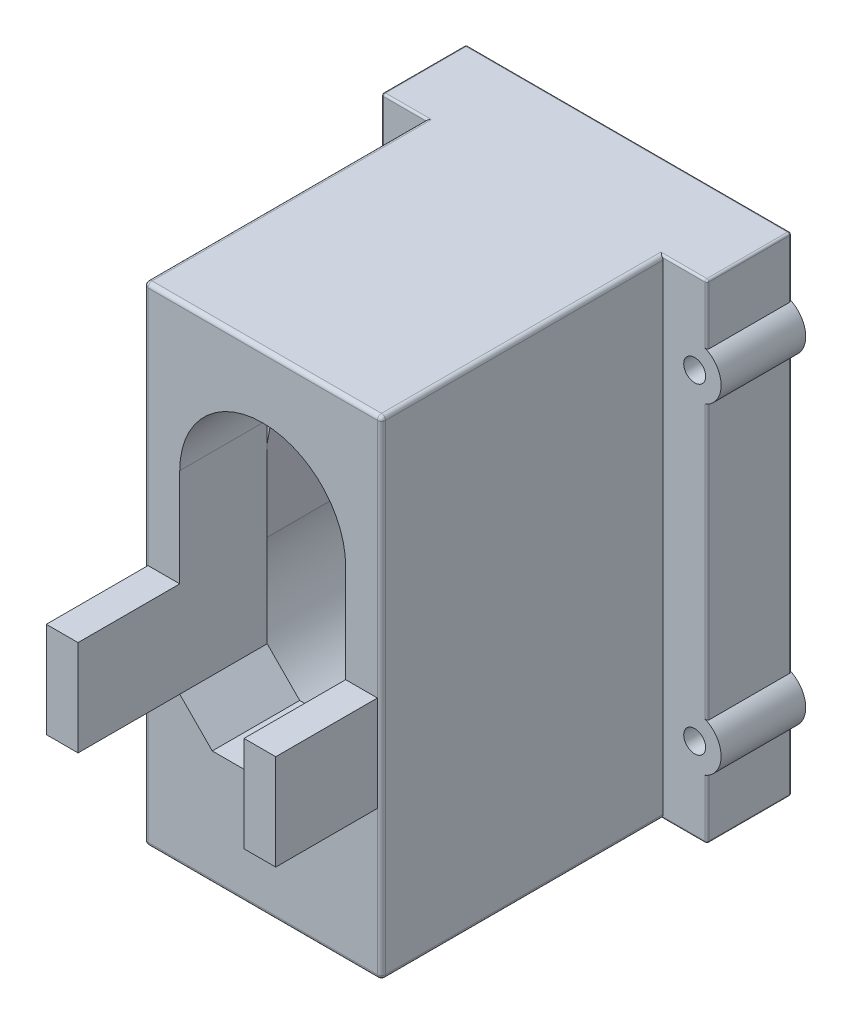
SolidWorks part; units mm, degrees
ref_plane "Plan de face" through (0, 0, 0) normal (0, 0, 1) x (1, 0, 0)
ref_plane "Plan de dessus" through (0, 0, 0) normal (0, 1, 0) x (1, 0, 0)
ref_plane "Plan de droite" through (0, 0, 0) normal (1, 0, 0) x (0, 0, -1)
sketch "Esquisse1" plane through (0, 0, 0) normal (0, 0, 1) x (1, 0, 0)
  line L0 (-4.8779, 36.0098) -> (-4.8779, -83.9902) construction
  line L1 (-44.8779, 36.0098) -> (35.1221, 36.0098)
  line L2 (-44.8779, 36.0098) -> (-44.8779, -83.9902)
  line L3 (-44.8779, -83.9902) -> (35.1221, -83.9902)
  line L4 (35.1221, 36.0098) -> (35.1221, -83.9902)
  dimension "D1" = 120
  dimension "D2" = 80
extrude "Boss.-Extru.1" add sketch "Esquisse1" along normal blind 90
sketch "Esquisse2" plane through (0, 0, 90) normal (0, 0, 1) x (1, 0, 0)
  line L0 (-4.8779, -83.9902) -> (-4.8779, 36.0098) construction
  line L1 (-44.8779, -83.9902) -> (35.1221, -83.9902) construction
  line L2 (35.1221, 36.0098) -> (-44.8779, 36.0098) construction
  line L3 (-25.2779, 0) -> (-25.2779, -47.5972)
  line L4 (15.5221, 0) -> (15.5221, -47.5972)
  line L5 (-4.8779, -55.6672) -> (7.5221, -55.6672)
  line L6 (-4.8779, -55.6672) -> (-17.2779, -55.6672)
  line L7 (15.5221, -47.5972) -> (7.5221, -55.6672)
  line L8 (-25.2779, -47.5972) -> (-17.2779, -55.6672)
  circle A0 centre (-4.8779, 0) radius 20.4
  dimension "D1" = 40.8
  dimension "D2" = 24.8
  dimension "D3" = 8.07
  dimension "D4" = 8.07
extrude "Enlèv. mat.-Extru.1" cut sketch "Esquisse2" against normal blind 21.5 contours L0 A0 | A0 L0 | L6 L0 A0 L3 L8 | L0 L5 L7 L4 A0 region at (-15.4138, -34.8601, 90) region at (5.658, -34.8601, 90) region at (-13.5359, 0, 90) region at (3.7801, 0, 90)
sketch "Esquisse3" plane through (0, 0, 68.5) normal (0, 0, 1) x (1, 0, 0)
  line L0 (-25.2779, 0) -> (15.5221, 0) construction
  line L1 (-4.8779, 0) -> (-4.8779, -55.6672) construction
  line L2 (-17.2779, -55.6672) -> (7.5221, -55.6672) construction
  line L3 (-24.3779, 0) -> (-29.6983, -29.3249)
  line L4 (14.6221, 0) -> (19.9425, -29.3249)
  circle A0 centre (-4.8779, 0) radius 19.5
  circle A1 centre (-4.8779, -36.7247) radius 25.9
  line M3 (-25.2779, 0) -> (-25.2779, -47.5972)
  line M4 (-25.2779, -47.5972) -> (-17.2779, -55.6672)
  line M5 (-17.2779, -55.6672) -> (7.5221, -55.6672)
  line M6 (7.5221, -55.6672) -> (15.5221, -47.5972)
  line M7 (15.5221, -47.5972) -> (15.5221, 0)
  dimension "D1" = 39
  dimension "D2" = 51.8
extrude "Enlèv. mat.-Extru.7" cut sketch "Esquisse3" against normal through all contours A1 A0 | A1 A0 L3 M3 | A0 A1 | A1 L3 M3 | A1 A0 M7 M3 M4 M5 M6 | A1 M7 M6 M5 M4 M3 | A1 L4 A0 M7 | A1 L4 M7 region at (-23.1117, -12.3273, 68.5) region at (-4.8779, 2.2509, 68.5) region at (-26.6699, -17.7509, 68.5) region at (13.356, -12.3273, 68.5) region at (-4.8779, -15.0342, 68.5) region at (-4.8779, -35.9109, 68.5) region at (-27.2977, -25.1442, 68.5) region at (16.9142, -17.7509, 68.5)
sketch "Esquisse4" plane through (0, 36.0098, 0) normal (0, 1, 0) x (1, 0, 0)
  line L0 (-44.8779, -90) -> (-44.8779, 0) construction
  line L1 (-44.8779, -20.8) -> (-34.0779, -20.8)
  line L2 (-44.8779, -20.8) -> (-44.8779, -90)
  line L3 (-44.8779, -90) -> (-34.0779, -90)
  line L4 (-34.0779, -20.8) -> (-34.0779, -90)
  line L5 (35.1221, -90) -> (-44.8779, -90) construction
  line L6 (35.1221, -90) -> (35.1221, 0) construction
  line L7 (35.1221, -20.8) -> (24.3221, -20.8)
  line L8 (35.1221, -20.8) -> (35.1221, -90)
  line L9 (35.1221, -90) -> (24.3221, -90)
  line L10 (24.3221, -20.8) -> (24.3221, -90)
  line L11 (35.1221, 0) -> (-44.8779, 0) construction
  dimension "D1" = 20.8
  dimension "D2" = 20.8
  dimension "D3" = 10.8
  dimension "D4" = 10.8
extrude "Enlèv. mat.-Extru.8" cut sketch "Esquisse4" against normal through all
sketch "Esquisse5" plane through (0, 0, 0) normal (0, 0, -1) x (-1, 0, 0)
  line L0 (-32.1221, 15.5098) -> (41.8779, 15.5098) construction
  line L1 (-35.1221, -83.9902) -> (-35.1221, 36.0098) construction
  line L2 (44.8779, 36.0098) -> (44.8779, -83.9902) construction
  line L3 (-35.1221, 36.0098) -> (44.8779, 36.0098) construction
  line L4 (-32.1221, -63.4902) -> (41.8779, -63.4902) construction
  line L5 (44.8779, -83.9902) -> (-35.1221, -83.9902) construction
  circle A0 centre (-32.1221, -63.4902) radius 2.7
  circle A1 centre (41.8779, -63.4902) radius 2.7
  circle A2 centre (-32.1221, 15.5098) radius 2.7
  circle A3 centre (41.8779, 15.5098) radius 2.7
  dimension "D7" = 5.4
  dimension "D8" = 5.4
  dimension "D9" = 5.4
  dimension "D10" = 5.4
  dimension "D1" = 3
  dimension "D2" = 3
  dimension "D3" = 20.5
  dimension "D4" = 20.5
  dimension "D5" = 3
  dimension "D6" = 3
extrude "Enlèv. mat.-Extru.9" cut sketch "Esquisse5" against normal through all
fillet "Congé1" radius 0.5 4 edges at (35.1221, -23.9902, 0) (-4.8779, 36.0098, 0) (-4.8779, -83.9902, 0) (-44.8779, -23.9902, 0)
fillet "Congé2" radius 0.5 14 edges at (34.9757, 35.8634, 0.1464) (34.9757, -83.8437, 0.1464) (-44.7314, -83.8437, 0.1464) (-44.7314, 35.8634, 0.1464) (35.1221, 36.0098, 10.65) (29.7221, 36.0098, 20.8) (29.7221, -83.9902, 20.8) (35.1221, -83.9902, 10.65) (35.1221, -23.9902, 20.8) (-39.4779, -83.9902, 20.8) (-44.8779, -83.9902, 10.65) (-44.8779, -23.9902, 20.8) (-44.8779, 36.0098, 10.65) (-39.4779, 36.0098, 20.8)
fillet "Congé3" radius 1 8 edges at (-34.0779, -83.9902, 55.15) (24.3221, -83.9902, 55.15) (-4.8779, -83.9902, 90) (-34.0779, -23.9902, 90) (-4.8779, 36.0098, 90) (24.3221, -23.9902, 90) (-34.0779, 36.0098, 55.15) (24.3221, 36.0098, 55.15)
sketch "Esquisse6" plane through (0, 0, 0) normal (0, 0, -1) x (-1, 0, 0)
  circle A0 centre (-32.1221, 15.5098) radius 6.5
  circle A1 centre (41.8779, 15.5098) radius 6.5
  circle A2 centre (41.8779, 15.5098) radius 2.7
  circle A3 centre (-32.1221, 15.5098) radius 2.7
  circle A4 centre (-32.1221, -63.4902) radius 6.5
  circle A5 centre (-32.1221, -63.4902) radius 2.7
  circle A6 centre (41.8779, -63.4902) radius 2.9997
  circle A7 centre (41.8779, -63.4902) radius 6.5
  dimension "D1" = 13
  dimension "D2" = 13
  dimension "D3" = 13
  dimension "D4" = 13
extrude "Boss.-Extru.2" add sketch "Esquisse6" against normal up to surface (20.8 mm away) up to face at (-39.1977, -23.9902, 20.8)
sketch "Esquisse7" plane through (0, 0, 90) normal (0, 0, 1) x (1, 0, 0)
  line L0 (-33.0779, 35.0098) -> (-33.0779, -82.9902) construction
  line L1 (-25.2779, -47.5972) -> (-33.0779, -47.5972)
  line L2 (-25.2779, -47.5972) -> (-25.2779, -24.0972)
  line L3 (-25.2779, -24.0972) -> (-33.0779, -24.0972)
  line L4 (-33.0779, -47.5972) -> (-33.0779, -24.0972)
  line L5 (23.3221, -82.9902) -> (23.3221, 35.0098) construction
  line L6 (15.5221, -47.5972) -> (23.3221, -47.5972)
  line L7 (15.5221, -47.5972) -> (15.5221, -24.0972)
  line L8 (15.5221, -24.0972) -> (23.3221, -24.0972)
  line L9 (23.3221, -47.5972) -> (23.3221, -24.0972)
  dimension "D1" = 23.5
  dimension "D2" = 23.5
extrude "Boss.-Extru.3" add sketch "Esquisse7" along normal blind 25
equation "\"0.5.00mm\"=10"
